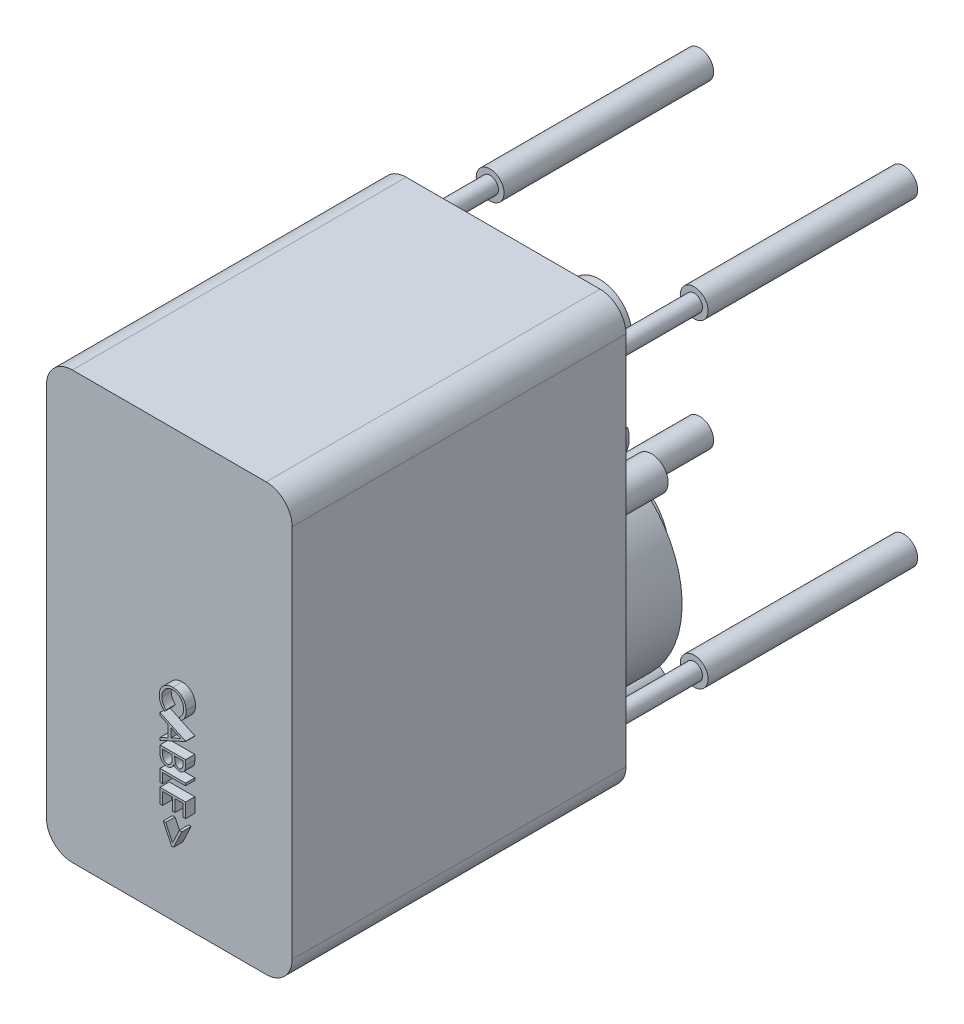
SolidWorks part; units mm, degrees
ref_plane "Front Plane" through (0, 0, 0) normal (0, 0, 1) x (1, 0, 0)
ref_plane "Top Plane" through (0, 0, 0) normal (0, 1, 0) x (1, 0, 0)
ref_plane "Right Plane" through (0, 0, 0) normal (1, 0, 0) x (0, 0, -1)
sketch "Sketch1" plane through (0, 0, 0) normal (0, 0, 1) x (1, 0, 0)
  line L0 (-13.081, 28.829) -> (13.081, 28.829)
  line L1 (-16.637, 25.273) -> (-16.637, -25.273)
  line L2 (-13.081, -28.829) -> (13.081, -28.829)
  line L3 (16.637, 25.273) -> (16.637, -25.273)
  line L4 (-16.637, 28.829) -> (16.637, -28.829) construction
  line L5 (-16.637, -28.829) -> (16.637, 28.829) construction
  line L6 (0, 36.9388) -> (0, -36.9388) construction
  line L7 (-21.0275, 0) -> (21.0275, 0) construction
  arc A0 (16.637, -25.273) -> (13.081, -28.829) centre (13.081, -25.273) cw
  arc A1 (-13.081, -28.829) -> (-16.637, -25.273) centre (-13.081, -25.273) cw
  arc A2 (16.637, 25.273) -> (13.081, 28.829) centre (13.081, 25.273) ccw
  arc A3 (-13.081, 28.829) -> (-16.637, 25.273) centre (-13.081, 25.273) ccw
  circle A4 centre (0, -12.7) radius 7.239
  circle A5 centre (0, 12.7) radius 4.445
  circle A6 centre (0, 14.605) radius 6.35
  circle A7 centre (0, -12.7) radius 14.351
  arc A8 (-3.6204, 1.1868) -> (3.6204, 1.1868) centre (0, 0) ccw
  circle A9 centre (13.97, 21.844) radius 1.016
  circle A10 centre (-13.97, 21.844) radius 1.016
  circle A11 centre (13.97, -21.844) radius 1.016
  circle A12 centre (-13.97, -21.844) radius 1.016
  arc A13 (6.6635, 0.0102) -> (10.0641, -2.4694) centre (8.89, -0.508) cw
  arc A14 (-10.0641, -2.4694) -> (-6.6635, 0.0102) centre (-8.89, -0.508) cw
  arc A15 (-10.0641, -22.9306) -> (-6.6635, -25.4102) centre (-8.89, -24.892) ccw
  arc A16 (6.6635, -25.4102) -> (10.0641, -22.9306) centre (8.89, -24.892) ccw
  point P0 (0, 0)
  dimension "D3" = 3.556
  dimension "D4" = 14.478
  dimension "D5" = 8.89
  dimension "D6" = 12.7
  dimension "D8" = 7.62
  dimension "D10" = 2.032
  dimension "D12" = 28.702
  dimension "D13" = 2.286
  dimension "D1" = 33.274
  dimension "D2" = 57.658
  dimension "D7" = 12.7
  dimension "D9" = 21.844
  dimension "D11" = 13.97
  dimension "D14" = 8.89
  dimension "D15" = 0.508
  dimension "D16" = 0.508
  dimension "D17" = 8.89
  dimension "D18" = 24.892
  dimension "D19" = 24.892
  dimension "D20" = 8.89
  dimension "D21" = 8.89
extrude "Boss-Extrude1" add sketch "Sketch1" against normal blind 10.16 contours A8 A7 A4 | A14 A7 | A7 A8 | A13 A7 | A7 A16 | A7 A15 | A4 region at (0, -12.7, 0) region at (12.8646, -18.0906, 0) region at (9.2197, -0.0559, 0) region at (9.2197, -25.3441, 0) region at (0, -0.8411, 0) region at (-9.2197, -25.3441, 0) region at (-9.2197, -0.0559, 0)
sketch "Sketch2" plane through (0, 0, 0) normal (0, 0, 1) x (1, 0, 0)
  line L0 (-13.081, 28.829) -> (13.081, 28.829)
  line L1 (-16.637, 25.273) -> (-16.637, -25.273)
  line L2 (-13.081, -28.829) -> (13.081, -28.829)
  line L3 (16.637, 25.273) -> (16.637, -25.273)
  line L4 (-16.637, 28.829) -> (16.637, -28.829) construction
  line L5 (-16.637, -28.829) -> (16.637, 28.829) construction
  line L6 (0, 38.9705) -> (0, -34.9071) construction
  line L7 (-9.8575, 0) -> (32.1974, 0) construction
  arc A0 (16.637, -25.273) -> (13.081, -28.829) centre (13.081, -25.273) cw
  arc A1 (-13.081, -28.829) -> (-16.637, -25.273) centre (-13.081, -25.273) cw
  arc A2 (16.637, 25.273) -> (13.081, 28.829) centre (13.081, 25.273) ccw
  arc A3 (-13.081, 28.829) -> (-16.637, 25.273) centre (-13.081, 25.273) ccw
  circle A4 centre (0, -12.7) radius 7.239
  circle A5 centre (0, 12.7) radius 4.445
  circle A6 centre (0, 14.605) radius 6.35
  circle A7 centre (0, -12.7) radius 14.351
  arc A8 (-3.6204, 1.1868) -> (3.6204, 1.1868) centre (0, 0) ccw
  circle A9 centre (13.97, 21.844) radius 1.016
  circle A10 centre (-13.97, 21.844) radius 1.016
  circle A11 centre (13.97, -21.844) radius 1.016
  circle A12 centre (-13.97, -21.844) radius 1.016
  arc A13 (6.6635, 0.0102) -> (10.0641, -2.4694) centre (8.89, -0.508) cw
  arc A14 (-10.0641, -2.4694) -> (-6.6635, 0.0102) centre (-8.89, -0.508) cw
  arc A15 (-10.0641, -22.9306) -> (-6.6635, -25.4102) centre (-8.89, -24.892) ccw
  arc A16 (6.6635, -25.4102) -> (10.0641, -22.9306) centre (8.89, -24.892) ccw
  point P0 (0, 0)
  dimension "D3" = 3.556
  dimension "D4" = 14.478
  dimension "D5" = 8.89
  dimension "D6" = 12.7
  dimension "D8" = 7.62
  dimension "D10" = 2.032
  dimension "D12" = 28.702
  dimension "D13" = 2.286
  dimension "D1" = 33.274
  dimension "D2" = 57.658
  dimension "D7" = 12.7
  dimension "D9" = 21.844
  dimension "D11" = 13.97
  dimension "D14" = 8.89
  dimension "D15" = 0.508
  dimension "D16" = 0.508
  dimension "D17" = 8.89
  dimension "D18" = 24.892
  dimension "D19" = 24.892
  dimension "D20" = 8.89
  dimension "D21" = 8.89
extrude "Boss-Extrude2" add sketch "Sketch2" against normal blind 1.778 separate body contours A5 | A5 A6 region at (0, 12.7, 0) region at (-4.3631, 18.9681, 0)
sketch "Sketch3" plane through (0, 0, -10.16) normal (0, 0, -1) x (-1, 0, 0)
  circle A0 centre (-8.89, -0.508) radius 2.286
  circle A1 centre (8.89, -24.892) radius 2.286
  circle A2 centre (-8.89, -24.892) radius 2.286
  circle A3 centre (8.89, -0.508) radius 2.286
extrude "Boss-Extrude3" add sketch "Sketch3" along normal blind 1.27
sketch "Sketch4" plane through (0, 0, -10.16) normal (0, 0, -1) x (-1, 0, 0)
  line L0 (-13.081, 28.829) -> (13.081, 28.829)
  line L1 (-16.637, 25.273) -> (-16.637, -25.273)
  line L2 (-13.081, -28.829) -> (13.081, -28.829)
  line L3 (16.637, 25.273) -> (16.637, -25.273)
  line L4 (-16.637, 28.829) -> (16.637, -28.829) construction
  line L5 (-16.637, -28.829) -> (16.637, 28.829) construction
  line L6 (0, 23.9866) -> (0, -49.891) construction
  line L7 (7.1619, 0) -> (49.2169, 0) construction
  arc A0 (16.637, -25.273) -> (13.081, -28.829) centre (13.081, -25.273) cw
  arc A1 (-13.081, -28.829) -> (-16.637, -25.273) centre (-13.081, -25.273) cw
  arc A2 (16.637, 25.273) -> (13.081, 28.829) centre (13.081, 25.273) ccw
  arc A3 (-13.081, 28.829) -> (-16.637, 25.273) centre (-13.081, 25.273) ccw
  circle A4 centre (0, -12.7) radius 7.239
  circle A5 centre (0, 12.7) radius 4.445
  circle A6 centre (0, 14.605) radius 6.35
  circle A7 centre (0, -12.7) radius 14.351
  arc A8 (-3.6204, 1.1868) -> (3.6204, 1.1868) centre (0, 0) ccw
  circle A9 centre (13.97, 21.844) radius 1.016
  circle A10 centre (-13.97, 21.844) radius 1.016
  circle A11 centre (13.97, -21.844) radius 1.016
  circle A12 centre (-13.97, -21.844) radius 1.016
  arc A13 (6.6635, 0.0102) -> (10.0641, -2.4694) centre (8.89, -0.508) cw
  arc A14 (-10.0641, -2.4694) -> (-6.6635, 0.0102) centre (-8.89, -0.508) cw
  arc A15 (-10.0641, -22.9306) -> (-6.6635, -25.4102) centre (-8.89, -24.892) ccw
  arc A16 (6.6635, -25.4102) -> (10.0641, -22.9306) centre (8.89, -24.892) ccw
  point P0 (0, 0)
  dimension "D3" = 3.556
  dimension "D4" = 14.478
  dimension "D5" = 8.89
  dimension "D6" = 12.7
  dimension "D8" = 7.62
  dimension "D10" = 2.032
  dimension "D12" = 28.702
  dimension "D13" = 2.286
  dimension "D1" = 33.274
  dimension "D2" = 57.658
  dimension "D7" = 12.7
  dimension "D9" = 21.844
  dimension "D11" = 13.97
  dimension "D14" = 8.89
  dimension "D15" = 0.508
  dimension "D16" = 0.508
  dimension "D17" = 8.89
  dimension "D18" = 24.892
  dimension "D19" = 24.892
  dimension "D20" = 8.89
  dimension "D21" = 8.89
extrude "Boss-Extrude4" add sketch "Sketch4" along normal blind 3.302 contours A7 A8 region at (0, -0.8411, -10.16)
sketch "Sketch5" plane through (0, 0, -1.778) normal (0, 0, -1) x (-1, 0, 0)
  line L0 (-13.081, 28.829) -> (13.081, 28.829)
  line L1 (-16.637, 25.273) -> (-16.637, -25.273)
  line L2 (-13.081, -28.829) -> (13.081, -28.829)
  line L3 (16.637, 25.273) -> (16.637, -25.273)
  line L4 (-16.637, 28.829) -> (16.637, -28.829) construction
  line L5 (-16.637, -28.829) -> (16.637, 28.829) construction
  line L6 (0, 36.0331) -> (0, -37.8445) construction
  line L7 (26.8703, 0) -> (68.9252, 0) construction
  arc A0 (16.637, -25.273) -> (13.081, -28.829) centre (13.081, -25.273) cw
  arc A1 (-13.081, -28.829) -> (-16.637, -25.273) centre (-13.081, -25.273) cw
  arc A2 (16.637, 25.273) -> (13.081, 28.829) centre (13.081, 25.273) ccw
  arc A3 (-13.081, 28.829) -> (-16.637, 25.273) centre (-13.081, 25.273) ccw
  circle A4 centre (0, -12.7) radius 7.239
  circle A5 centre (0, 12.7) radius 4.445
  circle A6 centre (0, 14.605) radius 6.35
  circle A7 centre (0, -12.7) radius 14.351
  arc A8 (-3.6204, 1.1868) -> (3.6204, 1.1868) centre (0, 0) ccw
  circle A9 centre (13.97, 21.844) radius 1.016
  circle A10 centre (-13.97, 21.844) radius 1.016
  circle A11 centre (13.97, -21.844) radius 1.016
  circle A12 centre (-13.97, -21.844) radius 1.016
  arc A13 (6.6635, 0.0102) -> (10.0641, -2.4694) centre (8.89, -0.508) cw
  arc A14 (-10.0641, -2.4694) -> (-6.6635, 0.0102) centre (-8.89, -0.508) cw
  arc A15 (-10.0641, -22.9306) -> (-6.6635, -25.4102) centre (-8.89, -24.892) ccw
  arc A16 (6.6635, -25.4102) -> (10.0641, -22.9306) centre (8.89, -24.892) ccw
  point P0 (0, 0)
  dimension "D3" = 3.556
  dimension "D4" = 14.478
  dimension "D5" = 8.89
  dimension "D6" = 12.7
  dimension "D8" = 7.62
  dimension "D10" = 2.032
  dimension "D12" = 28.702
  dimension "D13" = 2.286
  dimension "D1" = 33.274
  dimension "D2" = 57.658
  dimension "D7" = 12.7
  dimension "D9" = 21.844
  dimension "D11" = 13.97
  dimension "D14" = 8.89
  dimension "D15" = 0.508
  dimension "D16" = 0.508
  dimension "D17" = 8.89
  dimension "D18" = 24.892
  dimension "D19" = 24.892
  dimension "D20" = 8.89
  dimension "D21" = 8.89
extrude "Boss-Extrude5" add sketch "Sketch5" along normal blind 11.43 contours A5 region at (0, 12.7, -1.778)
sketch "Sketch6" plane through (0, 0, 0) normal (0, 0, 1) x (1, 0, 0)
  line L0 (-13.081, 28.829) -> (13.081, 28.829)
  line L1 (-16.637, 25.273) -> (-16.637, -25.273)
  line L2 (-13.081, -28.829) -> (13.081, -28.829)
  line L3 (16.637, 25.273) -> (16.637, -25.273)
  line L4 (-16.637, 28.829) -> (16.637, -28.829) construction
  line L5 (-16.637, -28.829) -> (16.637, 28.829) construction
  line L6 (0, 36.0885) -> (0, -37.789) construction
  line L7 (-47.9194, 0) -> (-5.8644, 0) construction
  arc A0 (16.637, -25.273) -> (13.081, -28.829) centre (13.081, -25.273) cw
  arc A1 (-13.081, -28.829) -> (-16.637, -25.273) centre (-13.081, -25.273) cw
  arc A2 (16.637, 25.273) -> (13.081, 28.829) centre (13.081, 25.273) ccw
  arc A3 (-13.081, 28.829) -> (-16.637, 25.273) centre (-13.081, 25.273) ccw
  circle A4 centre (0, -12.7) radius 7.239
  circle A5 centre (0, 12.7) radius 4.445
  circle A6 centre (0, 14.605) radius 6.35
  circle A7 centre (0, -12.7) radius 14.351
  arc A8 (-3.6204, 1.1868) -> (3.6204, 1.1868) centre (0, 0) ccw
  circle A9 centre (13.97, 21.844) radius 1.143
  circle A10 centre (-13.97, 21.844) radius 1.143
  circle A11 centre (13.97, -21.844) radius 1.143
  circle A12 centre (-13.97, -21.844) radius 1.143
  arc A13 (6.6635, 0.0102) -> (10.0641, -2.4694) centre (8.89, -0.508) cw
  arc A14 (-10.0641, -2.4694) -> (-6.6635, 0.0102) centre (-8.89, -0.508) cw
  arc A15 (-10.0641, -22.9306) -> (-6.6635, -25.4102) centre (-8.89, -24.892) ccw
  arc A16 (6.6635, -25.4102) -> (10.0641, -22.9306) centre (8.89, -24.892) ccw
  point P0 (0, 0)
  dimension "D3" = 3.556
  dimension "D4" = 14.478
  dimension "D5" = 8.89
  dimension "D6" = 12.7
  dimension "D8" = 7.62
  dimension "D10" = 2.286
  dimension "D12" = 28.702
  dimension "D13" = 2.286
  dimension "D1" = 33.274
  dimension "D2" = 57.658
  dimension "D7" = 12.7
  dimension "D9" = 21.844
  dimension "D11" = 13.97
  dimension "D14" = 8.89
  dimension "D15" = 0.508
  dimension "D16" = 0.508
  dimension "D17" = 8.89
  dimension "D18" = 24.892
  dimension "D19" = 24.892
  dimension "D20" = 8.89
  dimension "D21" = 8.89
extrude "Boss-Extrude6" add sketch "Sketch6" against normal blind 15.494 separate body contours A10 | A9 | A12 | A11 region at (13.97, 21.844, 0) region at (-13.97, 21.844, 0) region at (13.97, -21.844, 0) region at (-13.97, -21.844, 0)
sketch "Sketch7" plane through (0, 0, -10.16) normal (0, 0, -1) x (-1, 0, 0)
  line L0 (-13.081, 28.829) -> (13.081, 28.829)
  line L1 (-16.637, 25.273) -> (-16.637, -25.273)
  line L2 (-13.081, -28.829) -> (13.081, -28.829)
  line L3 (16.637, 25.273) -> (16.637, -25.273)
  line L4 (-16.637, 28.829) -> (16.637, -28.829) construction
  line L5 (-16.637, -28.829) -> (16.637, 28.829) construction
  line L6 (0, 26.9541) -> (0, -46.9235) construction
  line L7 (8.0915, 0) -> (50.1464, 0) construction
  arc A0 (16.637, -25.273) -> (13.081, -28.829) centre (13.081, -25.273) cw
  arc A1 (-13.081, -28.829) -> (-16.637, -25.273) centre (-13.081, -25.273) cw
  arc A2 (16.637, 25.273) -> (13.081, 28.829) centre (13.081, 25.273) ccw
  arc A3 (-13.081, 28.829) -> (-16.637, 25.273) centre (-13.081, 25.273) ccw
  circle A4 centre (0, -12.7) radius 7.239
  circle A5 centre (0, 12.7) radius 4.445
  circle A6 centre (0, 14.605) radius 6.35
  circle A7 centre (0, -12.7) radius 14.351
  arc A8 (-3.6204, 1.1868) -> (3.6204, 1.1868) centre (0, 0) ccw
  circle A9 centre (13.97, 21.844) radius 1.016
  circle A10 centre (-13.97, 21.844) radius 1.016
  circle A11 centre (13.97, -21.844) radius 1.016
  circle A12 centre (-13.97, -21.844) radius 1.016
  arc A13 (6.6635, 0.0102) -> (10.0641, -2.4694) centre (8.89, -0.508) cw
  arc A14 (-10.0641, -2.4694) -> (-6.6635, 0.0102) centre (-8.89, -0.508) cw
  arc A15 (-10.0641, -22.9306) -> (-6.6635, -25.4102) centre (-8.89, -24.892) ccw
  arc A16 (6.6635, -25.4102) -> (10.0641, -22.9306) centre (8.89, -24.892) ccw
  point P0 (0, 0)
  dimension "D3" = 3.556
  dimension "D4" = 14.478
  dimension "D5" = 8.89
  dimension "D6" = 12.7
  dimension "D8" = 7.62
  dimension "D10" = 2.032
  dimension "D12" = 28.702
  dimension "D13" = 2.286
  dimension "D1" = 33.274
  dimension "D2" = 57.658
  dimension "D7" = 12.7
  dimension "D9" = 21.844
  dimension "D11" = 13.97
  dimension "D14" = 8.89
  dimension "D15" = 0.508
  dimension "D16" = 0.508
  dimension "D17" = 8.89
  dimension "D18" = 24.892
  dimension "D19" = 24.892
  dimension "D20" = 8.89
  dimension "D21" = 8.89
extrude "Boss-Extrude7" add sketch "Sketch7" along normal blind 5.334 contours A4 region at (0, -12.7, -10.16)
sketch "Sketch8" plane through (0, 0, 0) normal (0, 0, 1) x (1, 0, 0)
  line L1 (-13.2715, 29.21) -> (13.2715, 29.21)
  line L2 (-16.8275, 25.654) -> (-16.8275, -25.654)
  line L3 (-13.2715, -29.21) -> (13.2715, -29.21)
  line L4 (16.8275, 25.654) -> (16.8275, -25.654)
  line L5 (-16.8275, 29.21) -> (16.8275, -29.21) construction
  line L6 (-16.8275, -29.21) -> (16.8275, 29.21) construction
  arc A8 (16.8275, -25.654) -> (13.2715, -29.21) centre (13.2715, -25.654) cw
  arc A13 (-13.2715, -29.21) -> (-16.8275, -25.654) centre (-13.2715, -25.654) cw
  arc A14 (16.8275, 25.654) -> (13.2715, 29.21) centre (13.2715, 25.654) ccw
  arc A15 (-13.2715, 29.21) -> (-16.8275, 25.654) centre (-13.2715, 25.654) ccw
  point P0 (0, 0)
  dimension "D3" = 3.556
  dimension "D1" = 33.655
  dimension "D23" = 58.42
extrude "Boss-Extrude8" add sketch "Sketch8" along normal blind 45.72
sketch "Sketch9" plane through (0, 0, -15.494) normal (0, 0, -1) x (-1, 0, 0)
  circle A0 centre (-13.97, 21.844) radius 1.905
  circle A1 centre (13.97, 21.844) radius 1.905
  circle A2 centre (13.97, -21.844) radius 1.905
  circle A3 centre (-13.97, -21.844) radius 1.905
  dimension "D1" = 3.81
extrude "Boss-Extrude9" add sketch "Sketch9" against normal blind 3.302 and the other way blind 25.4
sketch "Sketch10" plane through (0, 0, 45.72) normal (0, 0, 1) x (1, 0, 0)
  line L0 (0, 0) -> (0, -29.21) construction
  line L1 (-13.2715, -29.21) -> (13.2715, -29.21) construction
  text T0 "CABLE >"
extrude "Boss-Extrude10" add sketch "Sketch10" along normal blind 1.27
